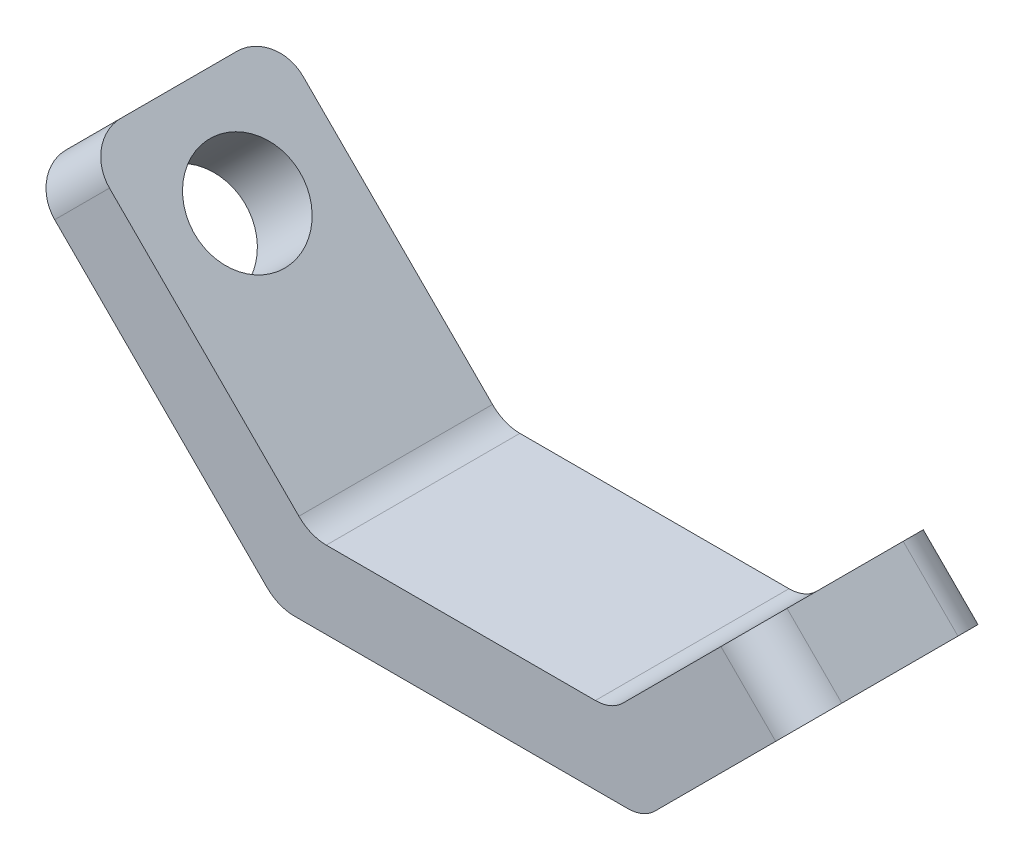
SolidWorks part; units mm, degrees
ref_plane "正面" through (0, 0, 0) normal (0, 0, 1) x (1, 0, 0)
ref_plane "平面" through (0, 0, 0) normal (0, 1, 0) x (1, 0, 0)
ref_plane "右側面" through (0, 0, 0) normal (1, 0, 0) x (0, 0, -1)
sketch "ｽｹｯﾁ1" plane through (0, 0, 0) normal (0, 0, 1) x (1, 0, 0)
  line L0 (0, 0) -> (-19.435, 19.435)
  line L1 (-19.435, 19.435) -> (-15.1924, 23.6777)
  line L2 (-15.1924, 23.6777) -> (2.4853, 6)
  line L3 (2.4853, 6) -> (25.8198, 6)
  line L4 (25.8198, 6) -> (36.4264, 16.6066)
  line L5 (36.4264, 16.6066) -> (40.669, 12.364)
  line L6 (40.669, 12.364) -> (28.3051, 0)
  line L7 (28.3051, 0) -> (0, 0)
  point P6 (31.1231, 11.3033)
  point P10 (-9.8891, 18.3744)
  dimension "D1" = 135
  dimension "D2" = 135
  dimension "D3" = 6
  dimension "D4" = 6
  dimension "D5" = 6
  dimension "D8" = 30
  dimension "D6" = 7.5
  dimension "D7" = 40
  dimension "D9" = 15
extrude "ﾎﾞｽ - 押し出し1" add sketch "ｽｹｯﾁ1" along normal mid plane 15
sketch "ｽｹｯﾁ2" plane through (0, 0, 0) normal (-0.7071, -0.7071, 0) x (0, 0, 1)
  line L0 (7.5, 2.4853) -> (7.5, 27.4853) construction
  line L1 (7.5, 27.4853) -> (-7.5, 27.4853) construction
  circle A0 centre (0, 19.9853) radius 4.1
  point P2 (0, 0)
  point P6 (7.5, 14.9853)
  dimension "D1" = 8.2
  dimension "D2" = 7.5
extrude "ｶｯﾄ - 押し出し1" cut sketch "ｽｹｯﾁ2" against normal through all both and the other way through all
sketch "ｽｹｯﾁ3" plane through (14.1525, -14.1525, 0) normal (0.7071, -0.7071, 0) x (0, 0, -1)
  line L0 (-7.5, 37.5) -> (-7.5, 22.5) construction
  line L1 (-7.5, 37.5) -> (7.5, 37.5) construction
  circle A0 centre (0, 30) radius 4.1
  point P4 (-7.5, 30)
  point P7 (0, 37.5)
  dimension "D1" = 8.2
extrude "ｶｯﾄ - 押し出し2" cut sketch "ｽｹｯﾁ3" against normal through all both and the other way through all
fillet "ﾌｨﾚｯﾄ1" radius 3 8 edges at (38.5477, 14.4853, -7.5) (38.5477, 14.4853, 7.5) (-17.3137, 21.5563, -7.5) (-17.3137, 21.5563, 7.5) (28.3051, 0, 0) (0, 0, 0) (25.8198, 6, 0) (2.4853, 6, 0)
equation "\"D4@ｽｹｯﾁ1\"=\"D3@ｽｹｯﾁ1\""
equation "\"D5@ｽｹｯﾁ1\"=\"D3@ｽｹｯﾁ1\""
